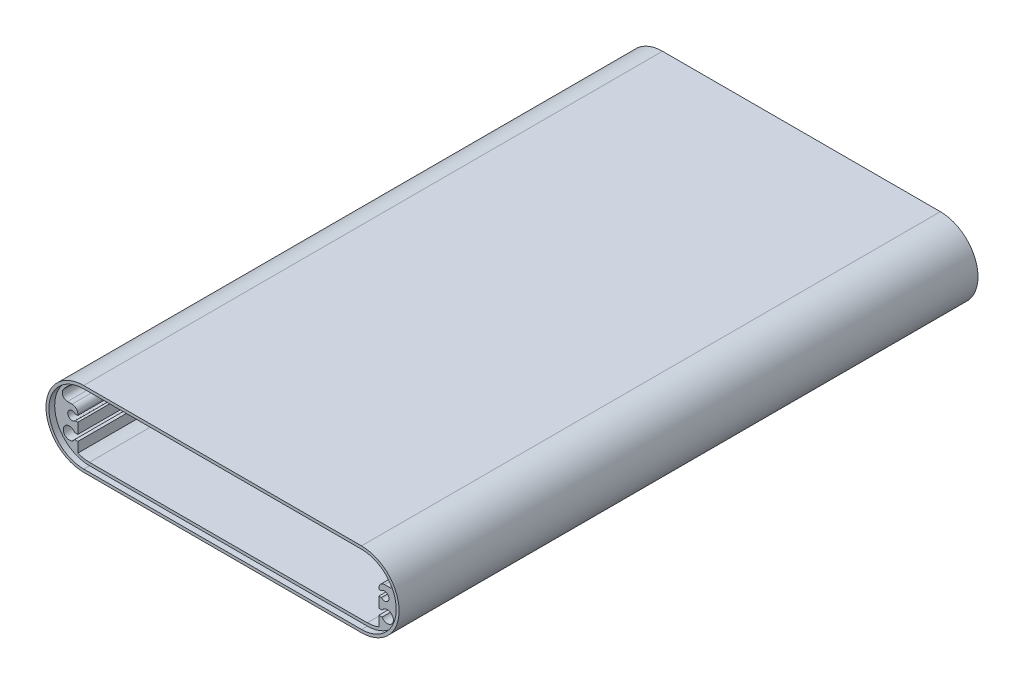
SolidWorks part; units mm, degrees
ref_plane "Front Plane" through (0, 0, 0) normal (0, 0, 1) x (1, 0, 0)
ref_plane "Top Plane" through (0, 0, 0) normal (0, 1, 0) x (1, 0, 0)
ref_plane "Right Plane" through (0, 0, 0) normal (1, 0, 0) x (0, 0, -1)
sketch "Sketch1" plane through (0, 0, 0) normal (0, 0, 1) x (1, 0, 0)
  line L0 (0, 0) -> (0, 16.0369) construction
  line L1 (30.5, 0) -> (-30.5, 0) construction
  line L2 (24, 6.5) -> (-24, 6.5)
  line L3 (24, -6.5) -> (-24, -6.5)
  line L4 (0, 0) -> (0, -11.8688) construction
  line L5 (24, 5.5) -> (-24, 5.5)
  line L6 (-24, -5.5) -> (24, -5.5)
  line L7 (27, 1.7) -> (27.7947, 1.7)
  line L8 (26, 0.5) -> (26, 0.7)
  line L9 (-26, -0.5) -> (-26.441, -0.5)
  line L10 (-26.441, 0.5) -> (-26, 0.5)
  line L11 (-26, -5.1235) -> (-26, -3.375)
  line L12 (-26, -3.375) -> (-26.5557, -3.375)
  line L13 (-26.5557, -2.325) -> (-26, -2.325)
  line L14 (-26, -2.325) -> (-26, -0.5)
  line L15 (-26, 0.5) -> (-26, 0.7)
  line L16 (-27, 1.7) -> (-27.7947, 1.7)
  line L17 (26, -2.325) -> (26, -0.5)
  line L18 (26.5557, -2.325) -> (26, -2.325)
  line L19 (26, -3.375) -> (26.5557, -3.375)
  line L20 (26, -5.1235) -> (26, -3.375)
  line L21 (26.441, 0.5) -> (26, 0.5)
  line L22 (26, -0.5) -> (26.441, -0.5)
  arc A0 (-24, 6.5) -> (-24, -6.5) centre (-24, 0) ccw
  arc A1 (-24, 5.5) -> (-28.5372, 3.1087) centre (-24, 0) ccw
  arc A2 (-26.5557, -2.325) -> (-26.5557, -3.375) centre (-27.465, -2.85) ccw
  arc A3 (-26.441, 0.5) -> (-26.441, -0.5) centre (-27, 0) ccw
  arc A4 (-27, 1.7) -> (-26, 0.7) centre (-27, 0.7) cw
  arc A5 (-26, -5.1235) -> (-24, -5.5) centre (-24, 0) ccw
  arc A6 (-27.7947, 1.7) -> (-28.5372, 3.1087) centre (-27.7947, 2.6) cw
  arc A7 (27.7947, 1.7) -> (28.5372, 3.1087) centre (27.7947, 2.6) ccw
  arc A8 (26, -5.1235) -> (24, -5.5) centre (24, 0) cw
  arc A9 (27, 1.7) -> (26, 0.7) centre (27, 0.7) ccw
  arc A10 (26.441, 0.5) -> (26.441, -0.5) centre (27, 0) cw
  arc A11 (26.5557, -2.325) -> (26.5557, -3.375) centre (27.465, -2.85) cw
  arc A12 (24, 5.5) -> (28.5372, 3.1087) centre (24, 0) cw
  arc A13 (24, 6.5) -> (24, -6.5) centre (24, 0) cw
  point P6 (0, 6.5)
  point P10 (0, -6.5)
  point P15 (0, 5.5)
  point P23 (-30.5, 0)
  point P56 (0, -5.5)
  dimension "D2" = 6.5
  dimension "D4" = 5.5
  dimension "D5" = 2.1
  dimension "D6" = 1.5
  dimension "D7" = 27
  dimension "D8" = 30.5
  dimension "D16" = 1
  dimension "D17" = 0.9
  dimension "D19" = 1.7
  dimension "D1" = 13
  dimension "D3" = 1
  dimension "D9" = 27.465
  dimension "D10" = 1
  dimension "D11" = 0.5
  dimension "D12" = 26
  dimension "D13" = 1.05
  dimension "D14" = 0.525
  dimension "D15" = 3.65
  dimension "D20" = 1
extrude "Boss-Extrude1" add sketch "Sketch1" along normal blind 50 and the other way blind 50
sketch "Sketch2" plane through (0, 0, 50) normal (0, 0, 1) x (1, 0, 0)
  line L0 (24, 6.5) -> (-24, 6.5) construction
  line L1 (-24, -6.5) -> (24, -6.5) construction
  line L2 (24, 6.5) -> (-24, 6.5) construction
  line L3 (-24, -6.5) -> (24, -6.5) construction
  line L4 (24, 6) -> (-24, 6)
  line L5 (-24, -6) -> (24, -6)
  arc A0 (-24, 6.5) -> (-24, -6.5) centre (-24, 0) ccw construction
  arc A1 (24, -6.5) -> (24, 6.5) centre (24, 0) ccw construction
  arc A2 (-24, 6.5) -> (-24, -6.5) centre (-24, 0) ccw construction
  arc A3 (24, -6.5) -> (24, 6.5) centre (24, 0) ccw construction
  arc A4 (-24, 6) -> (-24, -6) centre (-24, 0) ccw
  arc A5 (24, -6) -> (24, 6) centre (24, 0) ccw
  dimension "D1" = 0.5
extrude "Cut-Extrude1" cut sketch "Sketch2" against normal blind 1
mirror "Mirror1" about plane through (0, 0, 0) normal (0, 0, 1) of "Cut-Extrude1"
